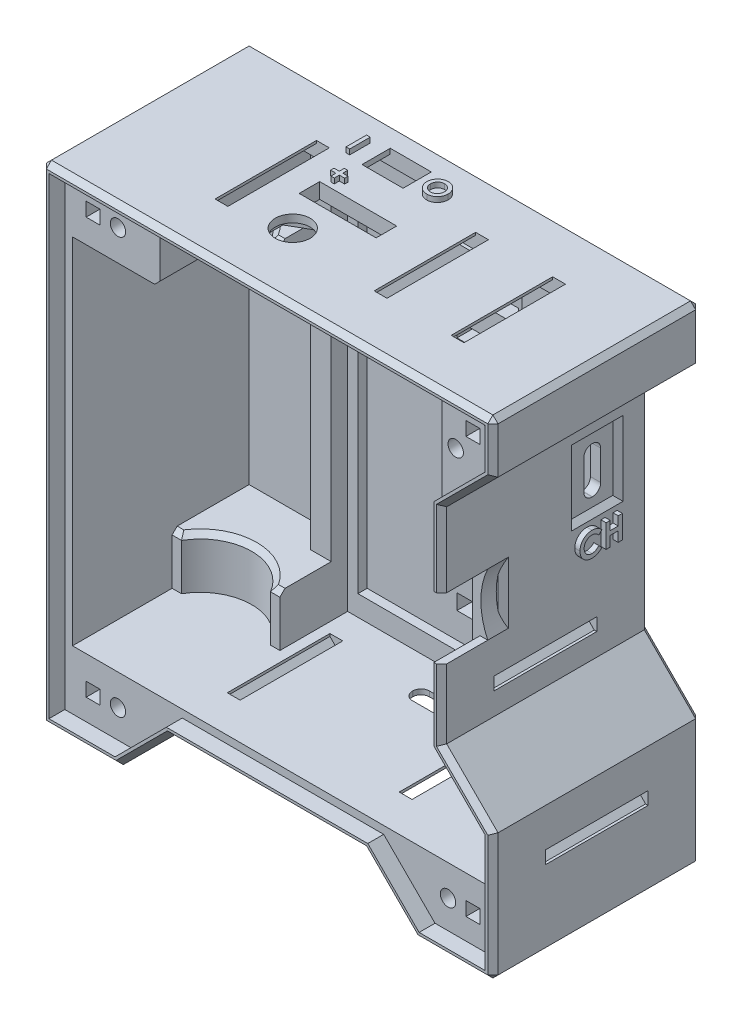
SolidWorks part; units mm, degrees
ref_plane "Front Plane" through (0, 0, 0) normal (0, 0, 1) x (1, 0, 0)
ref_plane "Top Plane" through (0, 0, 0) normal (0, 1, 0) x (1, 0, 0)
ref_plane "Right Plane" through (0, 0, 0) normal (1, 0, 0) x (0, 0, -1)
sketch "Sketch1" plane through (0, 0, 0) normal (0, 0, 1) x (1, 0, 0)
  line L0 (25, 10) -> (63, 10)
  line L1 (0, 0) -> (15, 0)
  line L2 (0, 0) -> (0, 95)
  line L3 (0, 95) -> (88, 95)
  line L4 (88, 0) -> (88, 25)
  line L5 (78, 75) -> (78, 35)
  line L6 (25, 10) -> (15, 0)
  line L7 (63, 10) -> (73, 0)
  line L8 (73, 0) -> (88, 0)
  line L9 (88, 85) -> (78, 75)
  line L10 (78, 35) -> (88, 25)
  line L11 (88, 85) -> (88, 95)
  dimension "D1" = 88
  dimension "D2" = 95
  dimension "D3" = 10
  dimension "D4" = 10
  dimension "D5" = 15
  dimension "D6" = 15
  dimension "D7" = 135
  dimension "D8" = 135
  dimension "D9" = 135
  dimension "D10" = 135
  dimension "D11" = 10
  dimension "D12" = 25
extrude "Boss-Extrude1" add sketch "Sketch1" along normal blind 40.5
sketch "Sketch2" plane through (0, 0, 40.5) normal (0, 0, 1) x (1, 0, 0)
  line L8 (3, 92) -> (85, 92)
  line L9 (85, 92) -> (85, 86.2426)
  line L10 (85, 86.2426) -> (75, 76.2426)
  line L11 (75, 76.2426) -> (75, 33.7574)
  line L12 (75, 33.7574) -> (85, 23.7574)
  line L13 (85, 23.7574) -> (85, 3)
  line L14 (85, 3) -> (74.2426, 3)
  line L15 (74.2426, 3) -> (64.2426, 13)
  line L16 (64.2426, 13) -> (23.7574, 13)
  line L17 (23.7574, 13) -> (13.7574, 3)
  line L18 (13.7574, 3) -> (3, 3)
  line L19 (3, 3) -> (3, 92)
  line L20 (0, 95) -> (0, 0) construction
  line L21 (78, 35) -> (78, 75) construction
  line L22 (25, 10) -> (63, 10) construction
  line L23 (88, 95) -> (0, 95) construction
  line L24 (73, 0) -> (88, 0) construction
  line L25 (0, 0) -> (15, 0) construction
  line L26 (63, 10) -> (73, 0) construction
  line L27 (15, 0) -> (25, 10) construction
  line L28 (88, 0) -> (88, 25) construction
  line L29 (88, 25) -> (78, 35) construction
  line L30 (78, 75) -> (88, 85) construction
  line L31 (88, 85) -> (88, 95) construction
  point P26 (68, 5)
  point P35 (83, 80)
  dimension "D1" = 3
  dimension "D2" = 3
  dimension "D3" = 3
  dimension "D4" = 3
  dimension "D5" = 3
  dimension "D6" = 3
  dimension "D7" = 3
  dimension "D8" = 3
  dimension "D9" = 3
  dimension "D10" = 3
  dimension "D11" = 3
  dimension "D12" = 3
extrude "Cut-Extrude1" cut sketch "Sketch2" against normal blind 37.5
sketch "Sketch3" plane through (0, 0, 40.5) normal (0, 0, 1) x (1, 0, 0)
  line L0 (1.5, 93.5) -> (86.5, 93.5)
  line L1 (86.5, 93.5) -> (86.5, 85.6213)
  line L2 (86.5, 85.6213) -> (76.5, 75.6213)
  line L3 (76.5, 75.6213) -> (76.5, 34.3787)
  line L4 (76.5, 34.3787) -> (86.5, 24.3787)
  line L5 (86.5, 24.3787) -> (86.5, 1.5)
  line L6 (86.5, 1.5) -> (73.6213, 1.5)
  line L7 (73.6213, 1.5) -> (63.6213, 11.5)
  line L8 (63.6213, 11.5) -> (24.3787, 11.5)
  line L9 (24.3787, 11.5) -> (14.3787, 1.5)
  line L10 (14.3787, 1.5) -> (1.5, 1.5)
  line L11 (1.5, 1.5) -> (1.5, 93.5)
  line L12 (88, 95) -> (0, 95) construction
  line L13 (0, 95) -> (0, 0) construction
  line L14 (0, 0) -> (15, 0) construction
  line L15 (15, 0) -> (25, 10) construction
  line L16 (25, 10) -> (63, 10) construction
  line L17 (63, 10) -> (73, 0) construction
  line L18 (73, 0) -> (88, 0) construction
  line L19 (88, 0) -> (88, 25) construction
  line L20 (88, 25) -> (78, 35) construction
  line L21 (78, 35) -> (78, 75) construction
  line L22 (78, 75) -> (88, 85) construction
  line L23 (88, 85) -> (88, 95) construction
  line L25 (85, 23.7574) -> (75, 33.7574) construction
  point P2 (1.8739, 93.2452)
  dimension "D1" = 1.5
  dimension "D2" = 1.5
  dimension "D3" = 1.5
  dimension "D4" = 1.5
  dimension "D5" = 1.5
  dimension "D6" = 1.5
  dimension "D7" = 1.5
  dimension "D8" = 1.5
  dimension "D9" = 1.5
  dimension "D10" = 1.5
  dimension "D11" = 1.5
  dimension "D12" = 1.5
extrude "Cut-Extrude2" cut sketch "Sketch3" against normal blind 3.1
sketch "Sketch4" plane through (0, 0, 40.5) normal (0, 0, 1) x (1, 0, 0)
  line L0 (78, 35) -> (78, 75) construction
  line L1 (78, 60.5) -> (76.5, 60.5)
  line L2 (78, 60.5) -> (78, 48.5)
  line L3 (78, 48.5) -> (76.5, 48.5)
  line L4 (75, 60.5) -> (75, 47.5)
  line L5 (75, 33.7574) -> (75, 76.2426) construction
  line L7 (88, 95) -> (0, 95) construction
  line L8 (76.5, 60.5) -> (75, 62)
  line L9 (75, 62) -> (75, 60.5)
  line L10 (76.5, 48.5) -> (75, 47)
  line L11 (75, 47) -> (75, 47.5)
  point P8 (78, 54.5)
  dimension "D1" = 12
  dimension "D2" = 40.5
  dimension "D3" = 45
  dimension "D4" = 45
  dimension "D5" = 1.5
  dimension "D6" = 1.5
extrude "Cut-Extrude3" cut sketch "Sketch4" against normal blind 9
sketch "Sketch5" plane through (78, 0, 0) normal (1, 0, 0) x (0, 0, -1)
  line L0 (0, 35) -> (0, 75) construction
  line L1 (-10.2, 70.5) -> (-10.1, 70.5)
  line L2 (-11.8, 68.9) -> (-11.8, 63.1)
  line L3 (-10.2, 61.5) -> (-10.1, 61.5)
  line L4 (-8.5, 68.9) -> (-8.5, 63.1)
  line L5 (-40.5, 0) -> (0, 0) construction
  arc A0 (-10.1, 61.5) -> (-8.5, 63.1) centre (-10.1, 63.1) ccw
  arc A1 (-11.8, 63.1) -> (-10.2, 61.5) centre (-10.2, 63.1) ccw
  arc A2 (-10.1, 70.5) -> (-8.5, 68.9) centre (-10.1, 68.9) cw
  arc A3 (-10.2, 70.5) -> (-11.8, 68.9) centre (-10.2, 68.9) ccw
  point P10 (-8.5, 61.5)
  point P13 (-11.8, 61.5)
  point P16 (-8.5, 70.5)
  dimension "D5" = 1.6
  dimension "D1" = 3.3
  dimension "D2" = 9
  dimension "D3" = 8.5
  dimension "D4" = 61.5
extrude "Cut-Extrude4" cut sketch "Sketch5" against normal blind 3
sketch "Sketch6" plane through (78, 0, 0) normal (1, 0, 0) x (0, 0, -1)
  line L0 (-11.8, 68.9) -> (-11.8, 63.1) construction
  line L1 (-14.15, 72.25) -> (-6.15, 72.25)
  line L2 (-14.15, 72.25) -> (-14.15, 59.75)
  line L3 (-14.15, 59.75) -> (-6.15, 59.75)
  line L4 (-6.15, 72.25) -> (-6.15, 59.75)
  line L5 (-10.1, 70.5) -> (-10.2, 70.5) construction
  point P6 (-11.8, 66)
  point P7 (-14.15, 66)
  point P10 (-10.15, 70.5)
  point P11 (-10.15, 72.25)
  dimension "D1" = 12.5
  dimension "D2" = 8
extrude "Cut-Extrude5" cut sketch "Sketch6" against normal blind 1
sketch "Sketch7" plane through (0, 0, 37.4) normal (0, 0, 1) x (1, 0, 0)
  line L0 (75, 33.7574) -> (75, 76.2426) construction
  line L1 (75, 61.5) -> (75.7, 61.5)
  line L2 (75, 61.5) -> (75, 70.5)
  line L3 (75, 70.5) -> (75.7, 70.5)
  line L4 (75.7, 61.5) -> (75.7, 70.5)
  line L5 (73, 0) -> (88, 0) construction
  dimension "D1" = 61.5
  dimension "D2" = 9
  dimension "D3" = 0.7
extrude "Cut-Extrude6" cut sketch "Sketch7" against normal blind 27.25
sketch "Sketch8" plane through (0, 95, 0) normal (0, 1, 0) x (1, 0, 0)
  line L0 (0, -40.5) -> (0, 0) construction
  line L1 (32, -4.5) -> (40, -4.5)
  line L2 (32, -4.5) -> (32, -10)
  line L3 (32, -10) -> (40, -10)
  line L4 (40, -4.5) -> (40, -10)
  line L5 (88, 0) -> (0, 0) construction
  line L7 (30.75, -17) -> (45.75, -17)
  line L8 (30.75, -17) -> (30.75, -21)
  line L9 (30.75, -21) -> (45.75, -21)
  line L10 (45.75, -17) -> (45.75, -21)
  dimension "D1" = 32
  dimension "D2" = 4.5
  dimension "D3" = 8
  dimension "D4" = 5.5
  dimension "D5" = 17
  dimension "D6" = 15
  dimension "D7" = 4
  dimension "D8" = 30.75
extrude "Cut-Extrude7" cut sketch "Sketch8" against normal blind 3
chamfer "Chamfer1" distance 2 angle 45 3 edges at (40, 92, 7.25) (32, 92, 7.25) (36, 92, 10)
sketch "Sketch9" plane through (0, 0, 3) normal (0, 0, 1) x (1, 0, 0)
  line L0 (75, 76.2426) -> (75, 92)
  line L1 (3, 92) -> (20, 92)
  line L2 (3, 92) -> (3, 82)
  line L3 (3, 82) -> (20, 82)
  line L4 (20, 92) -> (20, 82)
  line L5 (75, 92) -> (85, 92)
  line L6 (85, 92) -> (85, 86.2426)
  line L7 (85, 86.2426) -> (75, 76.2426)
  line L8 (64.2426, 13) -> (85, 13)
  line L9 (85, 3) -> (85, 23.7574) construction
  line L10 (85, 13) -> (85, 3)
  line L11 (85, 3) -> (74.2426, 3)
  line L12 (74.2426, 3) -> (64.2426, 13)
  line L13 (23.7574, 13) -> (3, 13)
  line L14 (3, 92) -> (3, 3) construction
  line L15 (3, 13) -> (3, 3)
  line L16 (3, 3) -> (13.7574, 3)
  line L17 (13.7574, 3) -> (23.7574, 13)
  dimension "D1" = 10
  dimension "D2" = 17
extrude "Boss-Extrude2" add sketch "Sketch9" along normal blind 34.4
sketch "Sketch10" plane through (0, 0, 37.4) normal (0, 0, 1) x (1, 0, 0)
  line L0 (0, 95) -> (0, 0) construction
  line L1 (7, 88) -> (81, 88) construction
  line L2 (7, 88) -> (7, 7) construction
  line L3 (7, 7) -> (81, 7) construction
  line L4 (81, 88) -> (81, 7) construction
  line L5 (7, 88) -> (81, 7) construction
  line L6 (7, 7) -> (81, 88) construction
  line L7 (88, 0) -> (88, 25) construction
  line L8 (0, 0) -> (15, 0) construction
  line L9 (88, 95) -> (0, 95) construction
  line L10 (79.65, 89.35) -> (82.35, 89.35)
  line L11 (5.65, 89.35) -> (8.35, 89.35)
  line L12 (5.65, 89.35) -> (5.65, 86.65)
  line L13 (5.65, 86.65) -> (8.35, 86.65)
  line L14 (8.35, 89.35) -> (8.35, 86.65)
  line L15 (5.65, 89.35) -> (8.35, 86.65) construction
  line L16 (5.65, 86.65) -> (8.35, 89.35) construction
  line L17 (79.65, 89.35) -> (79.65, 86.65)
  line L18 (79.65, 86.65) -> (82.35, 86.65)
  line L19 (82.35, 89.35) -> (82.35, 86.65)
  line L20 (79.65, 8.35) -> (82.35, 8.35)
  line L21 (79.65, 8.35) -> (79.65, 5.65)
  line L22 (79.65, 5.65) -> (82.35, 5.65)
  line L23 (82.35, 8.35) -> (82.35, 5.65)
  line L24 (5.65, 8.35) -> (8.35, 8.35)
  line L25 (5.65, 8.35) -> (5.65, 5.65)
  line L26 (5.65, 5.65) -> (8.35, 5.65)
  line L27 (8.35, 8.35) -> (8.35, 5.65)
  point P4 (44, 47.5)
  point P17 (7, 87.8723)
  point P18 (7, 86.65)
  point P19 (8.35, 88)
  point P24 (81, 86.65)
  point P25 (82.35, 88)
  point P26 (79.65, 88)
  point P31 (81, 8.35)
  point P32 (82.35, 7)
  point P33 (79.65, 7)
  point P38 (7, 5.65)
  point P39 (8.35, 7)
  point P40 (7, 8.35)
  dimension "D1" = 7
  dimension "D2" = 7
  dimension "D3" = 7
  dimension "D4" = 7
  dimension "D5" = 2.7
  dimension "D6" = 2.7
  dimension "D7" = 2.7
  dimension "D8" = 2.7
  dimension "D9" = 2.7
  dimension "D10" = 2.7
  dimension "D11" = 2.7
  dimension "D12" = 2.7
extrude "Cut-Extrude8" cut sketch "Sketch10" against normal blind 15
sketch "Sketch11" plane through (0, 10, 0) normal (0, -1, 0) x (1, 0, 0)
  line L0 (25, 0) -> (63, 0) construction
  line L1 (45.35, 13.55) -> (51.15, 13.55)
  line L2 (43.75, 11.95) -> (43.75, 11.85)
  line L3 (45.35, 10.25) -> (51.15, 10.25)
  line L4 (52.75, 11.95) -> (52.75, 11.85)
  line L5 (0, 40.5) -> (0, 0) construction
  arc A0 (51.15, 10.25) -> (52.75, 11.85) centre (51.15, 11.85) ccw
  arc A1 (51.15, 13.55) -> (52.75, 11.95) centre (51.15, 11.95) cw
  arc A2 (45.35, 13.55) -> (43.75, 11.95) centre (45.35, 11.95) ccw
  arc A3 (43.75, 11.85) -> (45.35, 10.25) centre (45.35, 11.85) ccw
  point P10 (52.75, 10.25)
  point P13 (52.75, 13.55)
  point P16 (43.75, 13.55)
  dimension "D5" = 1.6
  dimension "D1" = 3.3
  dimension "D2" = 9
  dimension "D3" = 10.25
  dimension "D4" = 43.75
extrude "Cut-Extrude9" cut sketch "Sketch11" against normal blind 3
sketch "Sketch12" plane through (0, 10, 0) normal (0, -1, 0) x (1, 0, 0)
  line L0 (43.75, 11.95) -> (43.75, 11.85) construction
  line L1 (41.75, 15.65) -> (54.75, 15.65)
  line L2 (41.75, 15.65) -> (41.75, 8.15)
  line L3 (41.75, 8.15) -> (54.75, 8.15)
  line L4 (54.75, 15.65) -> (54.75, 8.15)
  line L5 (45.35, 10.25) -> (51.15, 10.25) construction
  point P6 (43.75, 11.9)
  point P7 (41.75, 11.9)
  point P10 (48.25, 10.25)
  point P11 (48.25, 8.15)
  dimension "D1" = 13
  dimension "D2" = 7.5
extrude "Cut-Extrude10" cut sketch "Sketch12" against normal blind 2
sketch "Sketch13" plane through (0, 95, 0) normal (0, 1, 0) x (1, 0, 0)
  line L0 (0, -40.5) -> (0, 0) construction
  line L1 (88, 0) -> (0, 0) construction
  circle A0 centre (36, -27.5) radius 3.4
  dimension "D3" = 6.8
  dimension "D1" = 36
  dimension "D2" = 27.5
extrude "Cut-Extrude11" cut sketch "Sketch13" against normal blind 3
sketch "Sketch14" plane through (0, 92, 0) normal (0, -1, 0) x (1, 0, 0)
  line L1 (31.5, 24.9019) -> (36, 22.3038)
  line L2 (36, 22.3038) -> (40.5, 24.9019)
  line L3 (40.5, 24.9019) -> (40.5, 30.0981)
  line L4 (40.5, 30.0981) -> (36, 32.6962)
  line L5 (36, 32.6962) -> (31.5, 30.0981)
  line L6 (31.5, 30.0981) -> (31.5, 24.9019)
  circle A0 centre (36, 27.5) radius 4.5 construction
extrude "Cut-Extrude12" cut sketch "Sketch14" against normal blind 1.5
sketch "Sketch15" plane through (0, 0, 31.5) normal (0, 0, 1) x (1, 0, 0)
  line L0 (78, 48.5) -> (78, 60.5) construction
  line L1 (78, 60.5) -> (78, 48.5)
  arc A0 (78, 60.5) -> (78, 48.5) centre (90.6739, 54.5) ccw
extrude "Cut-Extrude13" cut sketch "Sketch15" against normal blind 3
chamfer "Chamfer2" distance 1 angle 45 1 edges at (78, 54.5, 28.5)
sketch "Sketch16" plane through (0, 0, 3) normal (0, 0, 1) x (1, 0, 0)
  line L0 (3, 13) -> (85, 13) construction
  line L1 (75, 92) -> (73, 92)
  line L2 (75, 92) -> (75, 13)
  line L3 (75, 13) -> (73, 13)
  line L4 (73, 80) -> (73, 17)
  line L5 (75, 92) -> (20, 92) construction
  line L6 (24, 92) -> (26, 92)
  line L7 (24, 92) -> (24, 13)
  line L8 (24, 13) -> (26, 13)
  line L9 (26, 92) -> (26, 17)
  line L10 (3, 13) -> (85, 13) construction
  line L12 (73, 13) -> (26, 13)
  line L14 (73, 17) -> (26, 17)
  line L16 (73, 92) -> (58, 92)
  line L18 (73, 80) -> (58, 80)
  line L19 (58, 92) -> (58, 80)
  dimension "D1" = 2
  dimension "D2" = 2
  dimension "D3" = 49
  dimension "D4" = 4
  dimension "D5" = 17
  dimension "D6" = 12
extrude "Boss-Extrude3" add sketch "Sketch16" along normal blind 1.8
sketch "Sketch17" plane through (0, 0, 3) normal (0, 0, 1) x (1, 0, 0)
  line L0 (3, 13) -> (85, 13) construction
  line L1 (24, 92) -> (20, 92)
  line L2 (24, 92) -> (24, 13)
  line L3 (24, 13) -> (20, 13)
  line L4 (20, 92) -> (20, 13)
  line L6 (75, 13) -> (78.5, 13)
  line L7 (75, 13) -> (75, 33.7574)
  line L8 (75, 33.7574) -> (78.5, 33.7574)
  line L9 (78.5, 13) -> (78.5, 33.7574)
  dimension "D1" = 3.5
extrude "Boss-Extrude4" add sketch "Sketch17" along normal blind 5
sketch "Sketch18" plane through (0, 0, 3) normal (0, 0, 1) x (1, 0, 0)
  line L0 (24, 92) -> (24, 13) construction
  line L1 (3, 82) -> (24, 82)
  line L2 (3, 82) -> (3, 76)
  line L3 (3, 76) -> (24, 76)
  line L4 (24, 82) -> (24, 76)
  line L6 (3, 13) -> (24, 13)
  line L7 (3, 13) -> (3, 23)
  line L8 (3, 23) -> (24, 23)
  line L9 (24, 13) -> (24, 23)
  dimension "D1" = 10
  dimension "D2" = 6
extrude "Boss-Extrude5" add sketch "Sketch18" along normal blind 15
sketch "Sketch19" plane through (0, 76, 0) normal (0, -1, 0) x (1, 0, 0)
  line L0 (13.5, 18) -> (13.5, 30.2316) construction
  line L1 (3, 18) -> (24, 18) construction
  line L2 (3, 3) -> (20, 3) construction
  circle A0 centre (13.5, 23) radius 10
  dimension "D1" = 20
  dimension "D2" = 20
extrude "Cut-Extrude14" cut sketch "Sketch19" against normal blind 6 and the other way blind 63
sketch "Sketch20" plane through (88, 0, 0) normal (1, 0, 0) x (0, 0, -1)
  line L0 (-40.5, 25) -> (0, 25) construction
  line L1 (-30.25, 20) -> (-10.25, 20)
  line L2 (-30.25, 20) -> (-30.25, 15)
  line L3 (-30.25, 15) -> (-10.25, 15)
  line L4 (-10.25, 20) -> (-10.25, 15)
  line L5 (-40.5, 0) -> (0, 0) construction
  line L6 (-40.5, 35) -> (0, 35) construction
  line L7 (-30.25, 39.3307) -> (-10.25, 39.3307)
  line L8 (-30.25, 39.3307) -> (-30.25, 44.3307)
  line L9 (-30.25, 44.3307) -> (-10.25, 44.3307)
  line L10 (-10.25, 39.3307) -> (-10.25, 44.3307)
  point P6 (-20.25, 25)
  point P7 (-20.25, 20)
  point P16 (-20.25, 35)
  point P17 (-20.25, 39.3307)
  dimension "D1" = 20
  dimension "D2" = 5
  dimension "D3" = 15
  dimension "D4" = 20
  dimension "D5" = 5
extrude "Cut-Extrude15" cut sketch "Sketch20" against normal blind 15
sketch "Sketch21" plane through (0, 95, 0) normal (0, 1, 0) x (1, 0, 0)
  line L0 (88, -40.5) -> (88, 0) construction
  line L1 (72, -10.3682) -> (67, -10.3682)
  line L2 (72, -10.3682) -> (72, -30.1318)
  line L3 (72, -30.1318) -> (67, -30.1318)
  line L4 (67, -10.3682) -> (67, -30.1318)
  line L5 (57, -10.3682) -> (52, -10.3682)
  line L6 (57, -10.3682) -> (57, -30.1318)
  line L7 (57, -30.1318) -> (52, -30.1318)
  line L8 (52, -10.3682) -> (52, -30.1318)
  line L9 (0, -40.5) -> (0, 0) construction
  line L10 (26, -10.3682) -> (21, -10.3682)
  line L11 (26, -10.3682) -> (26, -30.1318)
  line L12 (26, -30.1318) -> (21, -30.1318)
  line L13 (21, -10.3682) -> (21, -30.1318)
  point P10 (88, -20.25)
  point P11 (72, -20.25)
  point P12 (57, -20.25)
  point P19 (0, -20.25)
  point P20 (21, -20.25)
  dimension "D1" = 5
  dimension "D2" = 5
  dimension "D3" = 16
  dimension "D4" = 10
  dimension "D5" = 5
  dimension "D6" = 26
extrude "Cut-Extrude16" cut sketch "Sketch21" against normal blind 3
sketch "Sketch22" plane through (0, 10, 0) normal (0, -1, 0) x (1, 0, 0)
  line L0 (0, 40.5) -> (0, 0) construction
  line L1 (26, 30.25) -> (31, 30.25)
  line L2 (26, 30.25) -> (26, 10.25)
  line L3 (26, 10.25) -> (31, 10.25)
  line L4 (31, 30.25) -> (31, 10.25)
  line L5 (57, 30.25) -> (62, 30.25)
  line L6 (57, 30.25) -> (57, 10.25)
  line L7 (57, 10.25) -> (62, 10.25)
  line L8 (62, 30.25) -> (62, 10.25)
  line L9 (88, 40.5) -> (88, 0) construction
  point P10 (0, 20.25)
  point P11 (26, 20.25)
  point P12 (57, 20.25)
  dimension "D1" = 20
  dimension "D2" = 20
  dimension "D3" = 26
  dimension "D4" = 5
  dimension "D5" = 5
  dimension "D6" = 26
extrude "Cut-Extrude17" cut sketch "Sketch22" against normal blind 3
sketch "Sketch24" plane through (88, 0, 0) normal (1, 0, 0) x (0, 0, -1)
  line L6 (-10.25, 15) -> (-10.25, 20) construction
  line L7 (-30.25, 20) -> (-10.25, 20)
  line L8 (-30.25, 20) -> (-30.25, 17.5)
  line L9 (-30.25, 17.5) -> (-10.25, 17.5)
  line L10 (-10.25, 20) -> (-10.25, 17.5)
extrude "Boss-Extrude7" add sketch "Sketch24" against normal blind 1
sketch "Sketch25" plane through (0, 10, 0) normal (0, -1, 0) x (1, 0, 0)
  line L5 (57, 10.25) -> (62, 10.25) construction
  line L6 (62, 30.25) -> (59.5, 30.25)
  line L7 (62, 30.25) -> (62, 10.25)
  line L8 (62, 10.25) -> (59.5, 10.25)
  line L9 (59.5, 30.25) -> (59.5, 10.25)
  line L12 (31, 30.25) -> (26, 30.25) construction
  line L13 (26, 10.25) -> (28.5, 10.25)
  line L14 (26, 10.25) -> (26, 30.25)
  line L15 (26, 30.25) -> (28.5, 30.25)
  line L16 (28.5, 10.25) -> (28.5, 30.25)
extrude "Boss-Extrude8" add sketch "Sketch25" against normal blind 1
sketch "Sketch26" plane through (0, 95, 0) normal (0, 1, 0) x (1, 0, 0)
  line L0 (21, -30.1318) -> (26, -30.1318) construction
  line L1 (21, -10.3682) -> (23.5, -10.3682)
  line L2 (21, -10.3682) -> (21, -30.1318)
  line L3 (21, -30.1318) -> (23.5, -30.1318)
  line L4 (23.5, -10.3682) -> (23.5, -30.1318)
  line L5 (52, -30.1318) -> (57, -30.1318) construction
  line L6 (52, -10.3682) -> (54.5, -10.3682)
  line L7 (52, -10.3682) -> (52, -30.1318)
  line L8 (52, -30.1318) -> (54.5, -30.1318)
  line L9 (54.5, -10.3682) -> (54.5, -30.1318)
  line L10 (67, -30.1318) -> (72, -30.1318) construction
  line L11 (67, -10.3682) -> (69.5, -10.3682)
  line L12 (67, -10.3682) -> (67, -30.1318)
  line L13 (67, -30.1318) -> (69.5, -30.1318)
  line L14 (69.5, -10.3682) -> (69.5, -30.1318)
extrude "Boss-Extrude9" add sketch "Sketch26" against normal blind 1
sketch "Sketch27" plane through (0, 92, 0) normal (0, -1, 0) x (1, 0, 0)
  line L0 (26, 10.3682) -> (21, 10.3682) construction
  line L1 (26, 30.1318) -> (23.5, 30.1318)
  line L2 (26, 30.1318) -> (26, 10.3682)
  line L3 (26, 10.3682) -> (23.5, 10.3682)
  line L4 (23.5, 30.1318) -> (23.5, 10.3682)
  line L5 (57, 10.3682) -> (52, 10.3682) construction
  line L6 (57, 30.1318) -> (54.5, 30.1318)
  line L7 (57, 30.1318) -> (57, 10.3682)
  line L8 (57, 10.3682) -> (54.5, 10.3682)
  line L9 (54.5, 30.1318) -> (54.5, 10.3682)
  line L10 (72, 10.3682) -> (67, 10.3682) construction
  line L11 (72, 30.1318) -> (69.5, 30.1318)
  line L12 (72, 30.1318) -> (72, 10.3682)
  line L13 (72, 10.3682) -> (69.5, 10.3682)
  line L14 (69.5, 30.1318) -> (69.5, 10.3682)
extrude "Boss-Extrude10" add sketch "Sketch27" against normal blind 1
sketch "Sketch28" plane through (0, 13, 0) normal (0, 1, 0) x (1, 0, 0)
  line L1 (31, -10.25) -> (28.5, -10.25)
  line L2 (31, -10.25) -> (31, -30.25)
  line L3 (31, -30.25) -> (28.5, -30.25)
  line L4 (28.5, -10.25) -> (28.5, -30.25)
  line L9 (62, -30.25) -> (57, -30.25) construction
  line L10 (57, -10.25) -> (59.5, -10.25)
  line L11 (57, -10.25) -> (57, -30.25)
  line L12 (57, -30.25) -> (59.5, -30.25)
  line L13 (59.5, -10.25) -> (59.5, -30.25)
extrude "Boss-Extrude11" add sketch "Sketch28" against normal blind 1
sketch "Sketch30" plane through (85, 0, 0) normal (-1, 0, 0) x (0, 0, 1)
  line L0 (30.25, 20) -> (30.25, 15) construction
  line L1 (10.25, 15) -> (30.25, 15)
  line L2 (10.25, 15) -> (10.25, 17.5)
  line L3 (10.25, 17.5) -> (30.25, 17.5)
  line L4 (30.25, 15) -> (30.25, 17.5)
extrude "Boss-Extrude13" add sketch "Sketch30" against normal blind 1 contours L3 L4 L1 L2
chamfer "Chamfer3" distance 0.5 angle 45 4 edges at (54.5, 94, 20.25) (69.5, 94, 20.25) (69.5, 93, 20.25) (54.5, 93, 20.25)
chamfer "Chamfer6" distance 0.5 angle 45 4 edges at (28.5, 12, 20.25) (28.5, 11, 20.25) (59.5, 11, 20.25) (59.5, 12, 20.25)
sketch "Sketch31" plane through (78, 0, 0) normal (1, 0, 0) x (0, 0, -1)
  line L0 (-10.25, 44.3307) -> (-10.25, 39.3307) construction
  line L1 (-30.25, 44.3307) -> (-10.25, 44.3307)
  line L2 (-30.25, 44.3307) -> (-30.25, 41.8307)
  line L3 (-30.25, 41.8307) -> (-10.25, 41.8307)
  line L4 (-10.25, 44.3307) -> (-10.25, 41.8307)
extrude "Boss-Extrude14" add sketch "Sketch31" against normal blind 1
sketch "Sketch32" plane through (75, 0, 0) normal (-1, 0, 0) x (0, 0, 1)
  line L0 (30.25, 44.3307) -> (30.25, 39.3307) construction
  line L1 (10.25, 39.3307) -> (30.25, 39.3307)
  line L2 (10.25, 39.3307) -> (10.25, 41.8307)
  line L3 (10.25, 41.8307) -> (30.25, 41.8307)
  line L4 (30.25, 39.3307) -> (30.25, 41.8307)
extrude "Boss-Extrude15" add sketch "Sketch32" against normal blind 1
chamfer "Chamfer7" distance 0.5 angle 45 6 edges at (77, 41.8307, 20.25) (76, 41.8307, 20.25) (87, 17.5, 20.25) (86, 17.5, 20.25) (23.5, 94, 20.25) (23.5, 93, 20.25)
chamfer "Chamfer8" distance 1.5 angle 45 14 edges at (26, 93, 20.25) (57, 93, 20.25) (72, 93, 20.25) (76, 39.3307, 20.25) (86, 15, 20.25) (57, 12, 20.25) (31, 12, 20.25) (62, 11, 20.25) (26, 11, 20.25) (21, 94, 20.25) (52, 94, 20.25) (67, 94, 20.25) (77, 44.3307, 20.25) (87, 20, 20.25)
sketch "Sketch33" plane through (0, 0, 3) normal (0, 0, 1) x (1, 0, 0)
  line L0 (73, 17) -> (26, 17) construction
  line L1 (43.5, 22) -> (55.5, 22)
  line L2 (43.5, 22) -> (43.5, 25)
  line L3 (43.5, 25) -> (55.5, 25)
  line L4 (55.5, 22) -> (55.5, 25)
  line L5 (43.5, 30) -> (55.5, 30)
  line L6 (43.5, 30) -> (43.5, 33)
  line L7 (43.5, 33) -> (55.5, 33)
  line L8 (55.5, 30) -> (55.5, 33)
  line L9 (43.5, 38) -> (55.5, 38)
  line L10 (43.5, 38) -> (43.5, 41)
  line L11 (43.5, 41) -> (55.5, 41)
  line L12 (55.5, 38) -> (55.5, 41)
  line L13 (73, 17) -> (26, 17) construction
  line L14 (58, 92) -> (26, 92) construction
  line L15 (43.5, 68) -> (55.5, 68)
  line L16 (43.5, 68) -> (43.5, 71)
  line L17 (43.5, 71) -> (55.5, 71)
  line L18 (55.5, 68) -> (55.5, 71)
  line L19 (43.5, 76) -> (55.5, 76)
  line L20 (43.5, 76) -> (43.5, 79)
  line L21 (43.5, 79) -> (55.5, 79)
  line L22 (55.5, 76) -> (55.5, 79)
  line L23 (43.5, 84) -> (55.5, 84)
  line L24 (43.5, 84) -> (43.5, 87)
  line L25 (43.5, 87) -> (55.5, 87)
  line L26 (55.5, 84) -> (55.5, 87)
  point P14 (49.5, 17)
  point P15 (49.5, 38)
  point P16 (49.5, 30)
  point P17 (49.5, 22)
  point P32 (49.5, 41)
  point P33 (49.5, 68)
  point P34 (49.5, 76)
  point P35 (49.5, 84)
  dimension "D1" = 3
  dimension "D2" = 3
  dimension "D3" = 3
  dimension "D4" = 12
  dimension "D5" = 12
  dimension "D6" = 12
  dimension "D7" = 5
  dimension "D8" = 5
  dimension "D9" = 5
  dimension "D10" = 3
  dimension "D11" = 5
  dimension "D12" = 3
  dimension "D13" = 5
  dimension "D14" = 3
  dimension "D15" = 5
extrude "Cut-Extrude18" cut sketch "Sketch33" against normal blind 3
chamfer "Chamfer9" distance 1 angle 45 29 edges at (78, 67.75, 40.5) (83, 80, 40.5) (88, 90, 40.5) (78, 41.75, 40.5) (83, 30, 40.5) (88, 12.5, 40.5) (80.5, 0, 40.5) (68, 5, 40.5) (44, 10, 40.5) (20, 5, 40.5) (7.5, 0, 40.5) (0, 47.5, 40.5) (44, 95, 40.5) (0, 95, 20.25) (0, 0, 20.25) (88, 0, 20.25) (88, 95, 20.25) (44, 95, 0) (88, 90, 0) (83, 80, 0) (78, 55, 0) (83, 30, 0) (88, 12.5, 0) (80.5, 0, 0) (68, 5, 0) (44, 10, 0) (20, 5, 0) (7.5, 0, 0) (0, 47.5, 0)
sketch "Sketch34" plane through (0, 95, 0) normal (0, 1, 0) x (1, 0, 0)
  line L0 (28.0994, -9.5734) -> (48.0768, -9.5734) construction
  text T0 "I        O" font "Century Gothic" height 4
  point P3 (28.5791, -9.3933)
  point P4 (28.0994, -9.5734)
extrude "Boss-Extrude16" add sketch "Sketch34" along normal blind 1
sketch "Sketch35" plane through (78, 0, 0) normal (1, 0, 0) x (0, 0, -1)
  line L0 (-14.8201, 53.2851) -> (-4.1679, 53.2851) construction
  text T0 "CH" font "Century Gothic" height 4.5
  point P2 (-15.2146, 53.2569)
  point P3 (-4.1679, 53.2287)
  point P5 (-14.8201, 53.2851)
extrude "Boss-Extrude17" add sketch "Sketch35" along normal blind 1
sketch "Sketch36" plane through (0, 95, 0) normal (0, 1, 0) x (1, 0, 0)
  line L0 (30.5758, -16.5881) -> (34.0724, -16.5881) construction
  text T0 "+" font "Century Gothic" height 4
  point P3 (47.1019, -36.6015)
  point P4 (26.9839, -36.6901)
  point P7 (23.5274, -38.374)
  point P8 (24.5145, -38.3889)
  point P9 (25.7814, -38.4902)
extrude "Boss-Extrude18" add sketch "Sketch36" along normal blind 1
sketch "Sketch37" plane through (0, 10, 0) normal (0, -1, 0) x (1, 0, 0)
  line L0 (44.3209, 18.1608) -> (51.518, 18.1608) construction
  text T0 "PC" font "Century Gothic" height 4
  point P3 (37.6189, 17.281)
  point P4 (44.3209, 17.1829)
  point P5 (51.518, 17.0212)
extrude "Boss-Extrude19" add sketch "Sketch37" along normal blind 1
sketch "Sketch38" plane through (0, 0, 37.4) normal (0, 0, 1) x (1, 0, 0)
  line L0 (8.35, 5.65) -> (8.35, 8.35) construction
  line L1 (8.35, 86.65) -> (8.35, 89.35) construction
  line L2 (79.65, 86.65) -> (82.35, 86.65) construction
  line L3 (79.65, 89.35) -> (79.65, 86.65) construction
  line L4 (79.65, 8.35) -> (79.65, 5.65) construction
  line L5 (82.35, 86.65) -> (82.35, 89.35) construction
  line L6 (82.35, 89.35) -> (79.65, 89.35) construction
  circle A0 centre (11.85, 88) radius 1.5
  circle A1 centre (77.65, 83.65) radius 1.5
  circle A2 centre (76.15, 7) radius 1.5
  circle A3 centre (11.85, 7) radius 1.5
  circle A4 centre (84.35, 91.35) radius 1.5
  point P18 (79.65, 7)
  point P19 (8.35, 7)
  point P20 (8.35, 88)
  dimension "D1" = 3
  dimension "D2" = 3
  dimension "D3" = 3
  dimension "D4" = 3
  dimension "D10" = 2
  dimension "D5" = 3.5
  dimension "D6" = 3.5
  dimension "D7" = 3
  dimension "D8" = 2
  dimension "D9" = 3.5
  dimension "D11" = 2
extrude "Cut-Extrude19" cut sketch "Sketch38" against normal blind 21
chamfer "Chamfer10" distance 1 angle 45 1 edges at (20, 82, 26.4003)
chamfer "Chamfer11" distance 1 angle 45 8 edges at (13.5, 76, 13) (3.9199, 23, 18) (23.0801, 23, 18) (13.5, 23, 13) (3.9199, 76, 18) (23.0801, 76, 18) (21.1907, 82, 16.6084) (23.0801, 82, 18)
chamfer "Chamfer12" distance 1 angle 45 4 edges at (78, 72.25, 10.15) (78, 66, 14.15) (78, 59.75, 10.15) (78, 66, 6.15)
chamfer "Chamfer13" distance 1 angle 45 4 edges at (48.25, 10, 15.65) (41.75, 10, 11.9) (48.25, 10, 8.15) (54.75, 10, 11.9)
chamfer "Chamfer14" distance 1 angle 45 2 edges at (75.6, 61.5, 37.4) (75.35, 70.5, 37.4)
sketch "Sketch39" plane through (36.5, 36.5, 0) normal (-0.7071, -0.7071, 0) x (0, 0, 1)
  line L0 (0, -51.2046) -> (0, -37.0624) construction
  circle A0 centre (12, -44.5477) radius 3
  point P2 (0, 0)
  dimension "D1" = 12
extrude "Cut-Extrude20" cut sketch "Sketch39" against normal blind 15
sketch "Sketch40" plane through (0, 0, 8) normal (0, 0, 1) x (1, 0, 0)
  line L0 (20, 76) -> (20, 23) construction
  line L1 (20, 76) -> (24, 76)
  line L2 (20, 76) -> (20, 66)
  line L3 (20, 66) -> (24, 66)
  line L4 (24, 76) -> (24, 66)
  line L5 (24, 23) -> (24, 76) construction
  line L7 (20, 76) -> (24, 76) construction
  dimension "D1" = 10
extrude "Cut-Extrude21" cut sketch "Sketch40" against normal blind 2
chamfer "Chamfer15" distance 2 angle 45 1 edges at (22, 66, 8)
